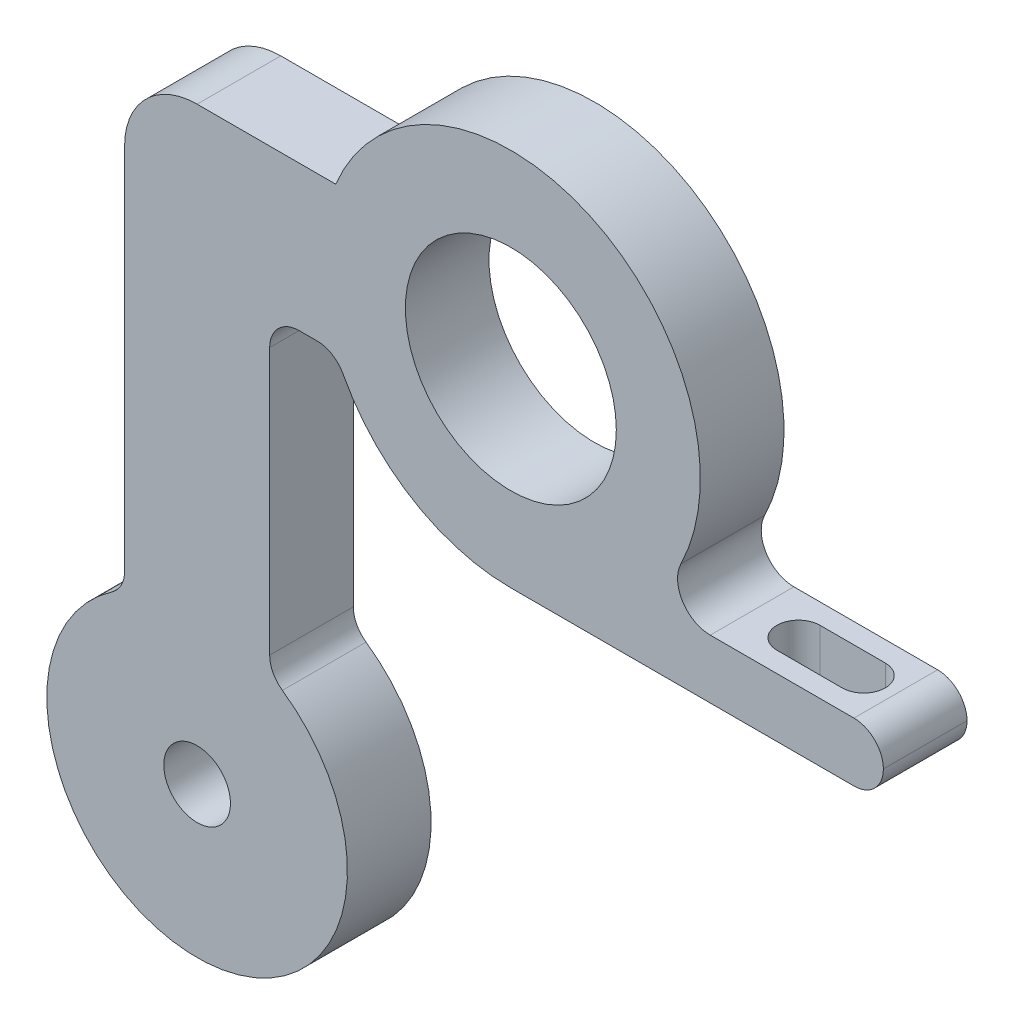
SolidWorks part; units mm, degrees
ref_plane "Front Plane" through (0, 0, 0) normal (0, 0, 1) x (1, 0, 0)
ref_plane "Top Plane" through (0, 0, 0) normal (0, 1, 0) x (1, 0, 0)
ref_plane "Right Plane" through (0, 0, 0) normal (1, 0, 0) x (0, 0, -1)
sketch "Sketch1" plane through (0, 0, 0) normal (0, 0, 1) x (1, 0, 0)
  line L0 (0, 0) -> (0, 39.5) construction
  line L1 (-5.55, 0) -> (-5.55, 39.5)
  line L2 (5.55, 0) -> (5.55, 39.5)
  line L3 (0, 39.5) -> (24, 39.5) construction
  line L4 (0, 45.05) -> (24, 45.05)
  line L5 (0, 33.95) -> (24, 33.95)
  line L6 (24, 25) -> (52.5, 25)
  line L7 (52.5, 25) -> (52.5, 29.5)
  line L8 (52.5, 29.5) -> (34.5, 29.5)
  line L9 (45.3, 29.5) -> (45.3, 25)
  line L10 (48.3, 29.5) -> (48.3, 25)
  line L11 (42.3, 29.5) -> (42.3, 25)
  line L12 (42.3, 27.25) -> (48.3, 27.25) construction
  circle A0 centre (0, 0) radius 2.55
  arc A1 (-5.55, 0) -> (5.55, 0) centre (0, 0) ccw
  arc A2 (5.55, 39.5) -> (-5.55, 39.5) centre (0, 39.5) ccw
  arc A3 (0, 45.05) -> (0, 33.95) centre (0, 39.5) ccw
  arc A4 (24, 33.95) -> (24, 45.05) centre (24, 39.5) ccw
  circle A5 centre (24, 39.5) radius 8.07
  circle A6 centre (24, 39.5) radius 14.5
  circle A7 centre (0, 0) radius 8
  circle A8 centre (0, 0) radius 11.5
  point P3 (0, 19.75)
  point P9 (12, 39.5)
  point P34 (45.3, 27.25)
  dimension "D1" = 5.1
  dimension "D5" = 16.14
  dimension "D6" = 29
  dimension "D7" = 16
  dimension "D8" = 23
  dimension "D2" = 3
  dimension "D3" = 39.5
  dimension "D4" = 24
  dimension "D9" = 4.5
  dimension "D10" = 21.3
  dimension "D11" = 18
  dimension "D12" = 6
extrude "Boss-Extrude3" add sketch "Sketch1" along normal blind 6.4 contours A3 L1 A1 L2 L5 A0 | A2 A3 L5 L2 | A6 L4 A2 L2 L5 | L4 A6 L5 A5 | L5 A6 L4 A5 | L1 A8 L2 A7 | L2 A8 L1 A7 | A6 L6 L11 L8 | L8 L11 L6 L9 | L10 L8 L9 L6 | L8 L10 L6 L7 | L1 A7 L2 A1 | L2 A7 L1 A1 A0 region at (0, -5.761, 0) region at (-5.3748, 2.8809, 0) region at (-3.2539, -7.6523, 0) region at (0, 9.1362, 0) region at (-0.1092, 22.8111, 0) region at (0.2756, 39.2244, 0) region at (7.305, 40.023, 0) region at (26.7509, 53.3266, 0) region at (13.2644, 39.5, 0) region at (36.5072, 26.972, 0) region at (43.8, 27.25, 0) region at (46.8, 27.25, 0) region at (50.4, 27.25, 0)
sketch "Sketch2" plane through (0, 29.5, 0) normal (0, 1, 0) x (1, 0, 0)
  line L0 (45.3, 0) -> (45.3, -6.4) construction
  line L2 (42.8, -3.2) -> (47.8, -3.2) construction
  line L3 (42.8, -1.55) -> (47.8, -1.55)
  line L4 (42.8, -4.85) -> (47.8, -4.85)
  line L5 (52.5, -6.4) -> (34.5, -6.4) construction
  arc A1 (42.8, -1.55) -> (42.8, -4.85) centre (42.8, -3.2) ccw
  arc A2 (47.8, -4.85) -> (47.8, -1.55) centre (47.8, -3.2) ccw
  point P3 (45.3, -5.7651)
  point P7 (45.3, -3.2)
  point P13 (0, 0)
  dimension "D2" = 1.65
  dimension "D1" = 5
extrude "Cut-Extrude1" cut sketch "Sketch2" against normal blind 16
fillet "Fillet1" radius 2.5 1 edges at (34.5, 29.5, 3.2)
fillet "Fillet2" radius 2.25 6 edges at (10.6042, 33.95, 3.2) (-5.55, 10.0721, 3.2) (5.55, 10.0721, 3.2) (5.55, 33.95, 3.2) (52.5, 25, 3.2) (52.5, 29.5, 3.2)
